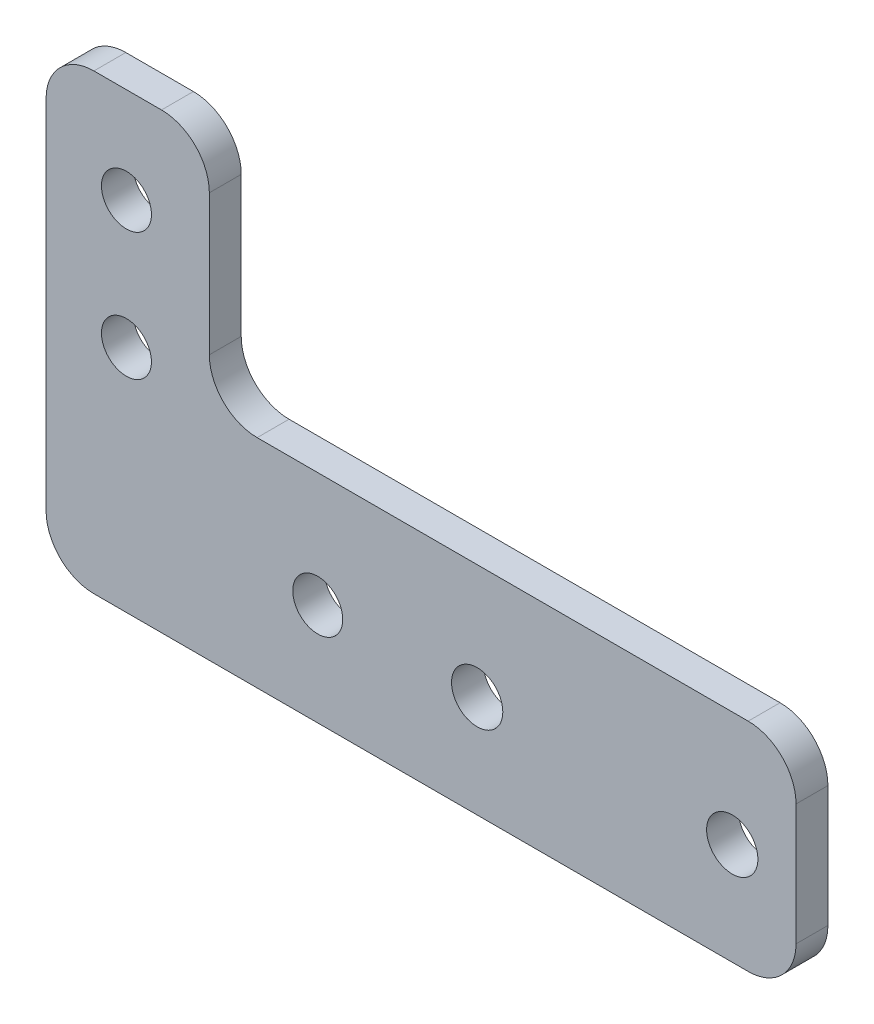
SolidWorks part; units mm, degrees
material "6061-T6 (SS)"
ref_plane "Front Plane" through (0, 0, 0) normal (0, 0, 1) x (1, 0, 0)
ref_plane "Top Plane" through (0, 0, 0) normal (0, 1, 0) x (1, 0, 0)
ref_plane "Right Plane" through (0, 0, 0) normal (1, 0, 0) x (0, 0, -1)
sketch "Sketch1" plane through (0, 0, 0) normal (0, 0, 1) x (1, 0, 0)
  line L0 (-17.145, 23.8125) -> (-33.401, 23.8125) construction
  line L1 (-41.275, -23.8125) -> (41.275, -23.8125)
  line L2 (-41.275, -23.8125) -> (-41.275, 23.8125)
  line L3 (-41.275, 23.8125) -> (41.275, 23.8125)
  line L4 (41.275, -23.8125) -> (41.275, 23.8125)
  line L5 (-41.275, -23.8125) -> (41.275, 23.8125) construction
  line L6 (-41.275, 23.8125) -> (41.275, -23.8125) construction
  line L7 (41.275, 23.8125) -> (-17.145, 23.8125)
  line L8 (41.275, 23.8125) -> (41.275, 0.3175)
  line L9 (41.275, 0.3175) -> (-17.145, 0.3175)
  line L10 (-17.145, 23.8125) -> (-17.145, 0.3175)
  line L11 (-41.275, -23.8125) -> (-33.401, -23.8125)
  line L12 (-41.275, -23.8125) -> (-41.275, 23.8125)
  line L13 (-41.275, 23.8125) -> (-33.401, 23.8125)
  line L14 (-33.401, -23.8125) -> (-33.401, 23.8125)
  line L15 (-33.401, -23.8125) -> (41.275, -23.8125)
  line L16 (-33.401, -23.8125) -> (-33.401, -21.2725)
  line L17 (-33.401, -21.2725) -> (41.275, -21.2725)
  line L18 (41.275, -23.8125) -> (41.275, -21.2725)
  circle A0 centre (-25.4, -11.1125) radius 2.4892
  circle A1 centre (-25.4, 1.5875) radius 2.4892
  circle A2 centre (-25.4, 14.2875) radius 2.4892
  circle A4 centre (-6.35, -11.1125) radius 2.4892
  circle A5 centre (9.525, -11.1125) radius 2.5527
  circle A7 centre (34.925, -11.1125) radius 2.5527
  point P0 (0, 0)
  point P24 (0, 0)
  dimension "D7" = 19.05
  dimension "D18" = 5.1054
  dimension "D19" = 4.9784
  dimension "D13" = 25.4
  dimension "D1" = 82.55
  dimension "D2" = 9.525
  dimension "D3" = 24.13
  dimension "D4" = 24.13
  dimension "D5" = 7.874
  dimension "D6" = 47.625
  dimension "D8" = 15.875
  dimension "D9" = 12.7
  dimension "D10" = 12.7
  dimension "D11" = 12.7
  dimension "D12" = 8.001
  dimension "D14" = 27.051
  dimension "D15" = 15.875
  dimension "D16" = 2.54
extrude "Boss-Extrude1" add sketch "Sketch1" along normal blind 3.175 contours L14 L17 L4 L9 L10 L3 A5 A4 A2 A1 A0 | A0 region at (-1.3908, -6.2418, 0) region at (-25.4, -11.1125, 0)
fillet "Fillet1" radius 4.7625 6 edges at (-33.401, 23.8125, 1.5875) (-17.145, 23.8125, 1.5875) (-17.145, 0.3175, 1.5875) (41.275, 0.3175, 1.5875) (41.275, -21.2725, 1.5875) (-33.401, -21.2725, 1.5875)
